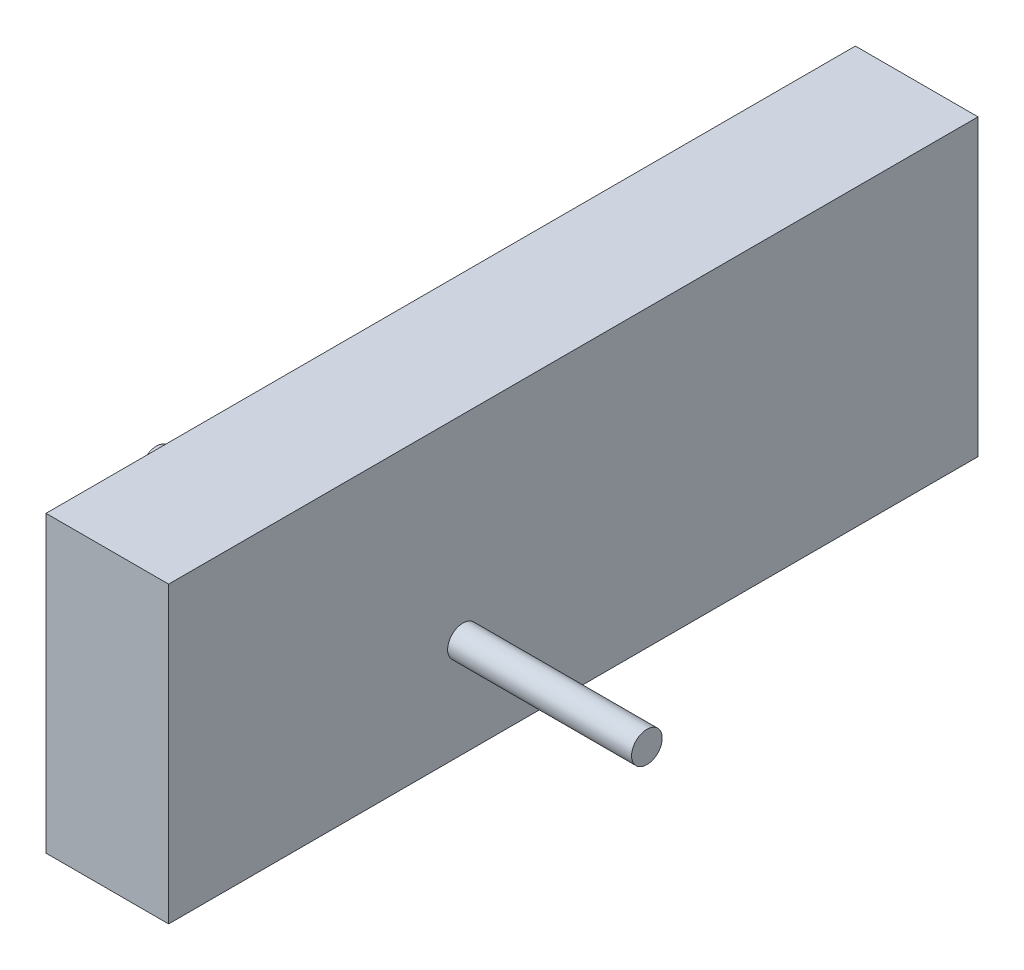
SolidWorks part; units mm, degrees
material "Custom Plastic"
ref_plane "Front Plane" through (0, 0, 0) normal (0, 0, 1) x (1, 0, 0)
ref_plane "Top Plane" through (0, 0, 0) normal (0, 1, 0) x (1, 0, 0)
ref_plane "Right Plane" through (0, 0, 0) normal (1, 0, 0) x (0, 0, -1)
sketch "Sketch1" plane through (0, 0, 0) normal (1, 0, 0) x (0, 0, -1)
  circle A0 centre (0, 0) radius 7.9375
  dimension "D1" = 15.875
extrude "Boss-Extrude1" add sketch "Sketch1" along normal mid plane 254
sketch "Sketch2" plane through (0, 0, 0) normal (1, 0, 0) x (0, 0, -1)
  line L1 (-152.4, -50.8) -> (266.7, -50.8)
  line L2 (-152.4, -50.8) -> (-152.4, 101.6)
  line L3 (-152.4, 101.6) -> (266.7, 101.6)
  line L4 (266.7, -50.8) -> (266.7, 101.6)
  dimension "D1" = 152.4
  dimension "D2" = 419.1
  dimension "D3" = 50.8
  dimension "D4" = 152.4
extrude "Boss-Extrude2" add sketch "Sketch2" along normal mid plane 63.5
